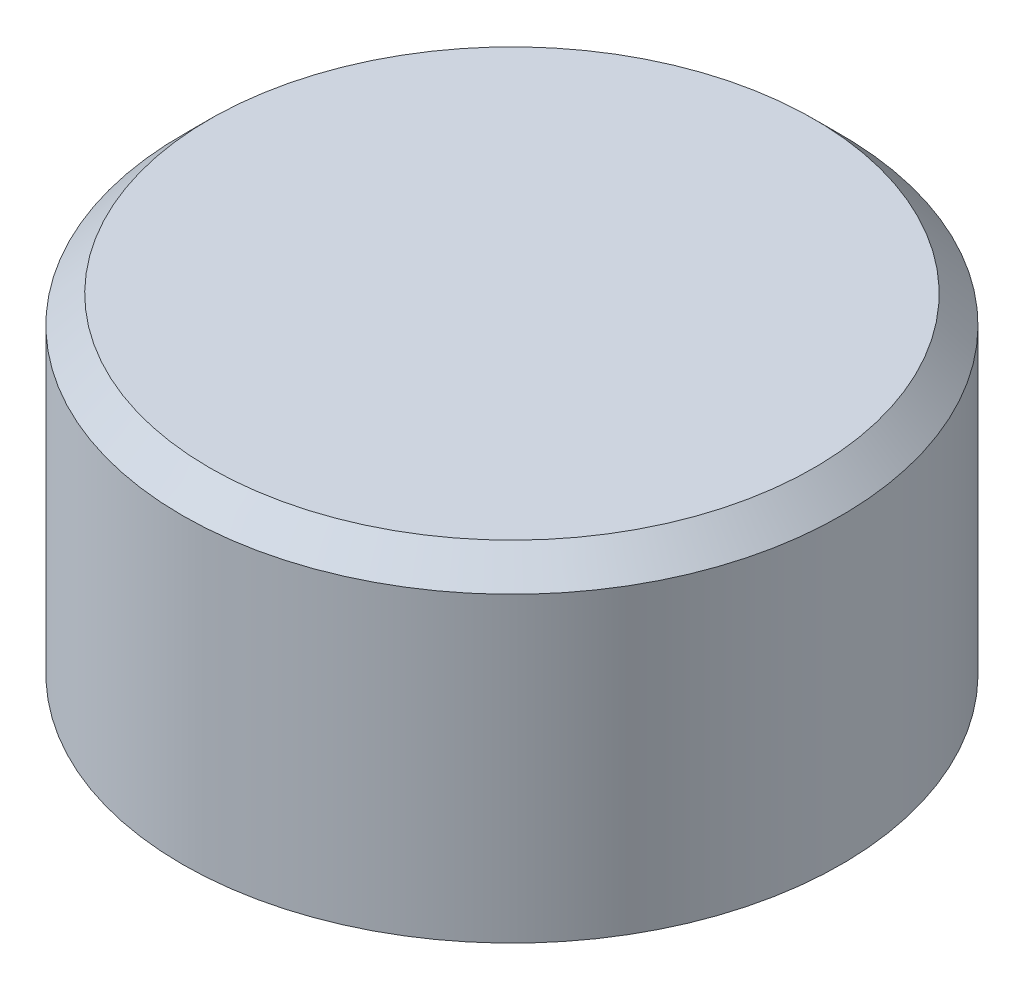
SolidWorks part; units mm, degrees
ref_plane "Front Plane" through (0, 0, 0) normal (0, 0, 1) x (1, 0, 0)
ref_plane "Top Plane" through (0, 0, 0) normal (0, 1, 0) x (1, 0, 0)
ref_plane "Right Plane" through (0, 0, 0) normal (1, 0, 0) x (0, 0, -1)
sketch "Sketch1" plane through (0, 0, 0) normal (0, 1, 0) x (1, 0, 0)
  circle A0 centre (0, 0) radius 6
  dimension "D1" = 12
extrude "Boss-Extrude1" add sketch "Sketch1" along normal blind 6
sketch "Sketch2" plane through (0, 0, 0) normal (0, -1, 0) x (1, 0, 0)
  circle A0 centre (0, 0) radius 2.75
  dimension "D1" = 5.5
extrude "Cut-Extrude1" cut sketch "Sketch2" against normal blind 5
chamfer "Chamfer1" distance 0.5 angle 45 1 edges at (0, 0, -2.75)
thread "Thread1" pitch 1 method cut profile "Thread Profile1" start angle 0, offset 1, length 0, pitch 1, diameter 5.5
ref_plane "Plane1" through (2.75, -0.5, 0) normal (0, 0, 1) x (1, 0, 0)
sketch "Thread Profile1" plane through (2.75, -0.5, 0) normal (0, 0, 1) x (1, 0, 0)
  line L0 (0, 0) -> (0, 1) construction
  line L1 (0, 0) -> (0.5413, 0.3125)
  line L2 (0.5413, 0.3125) -> (0.5413, 0.4375)
  line L3 (0.5413, 0.4375) -> (0, 0.75)
  line L4 (0.5413, 0.375) -> (0, 0.375) construction
  line L11 (0, 0) -> (0, 0.75)
  point P2 (0, 0)
  dimension "Pitch" = 1
  dimension "Profile_Angle" = 60
  dimension "Profile_Land" = 0.125
  dimension "Profile_Height" = 0.5413
chamfer "Chamfer2" distance 0.5 angle 45 1 edges at (0, 6, 6)
